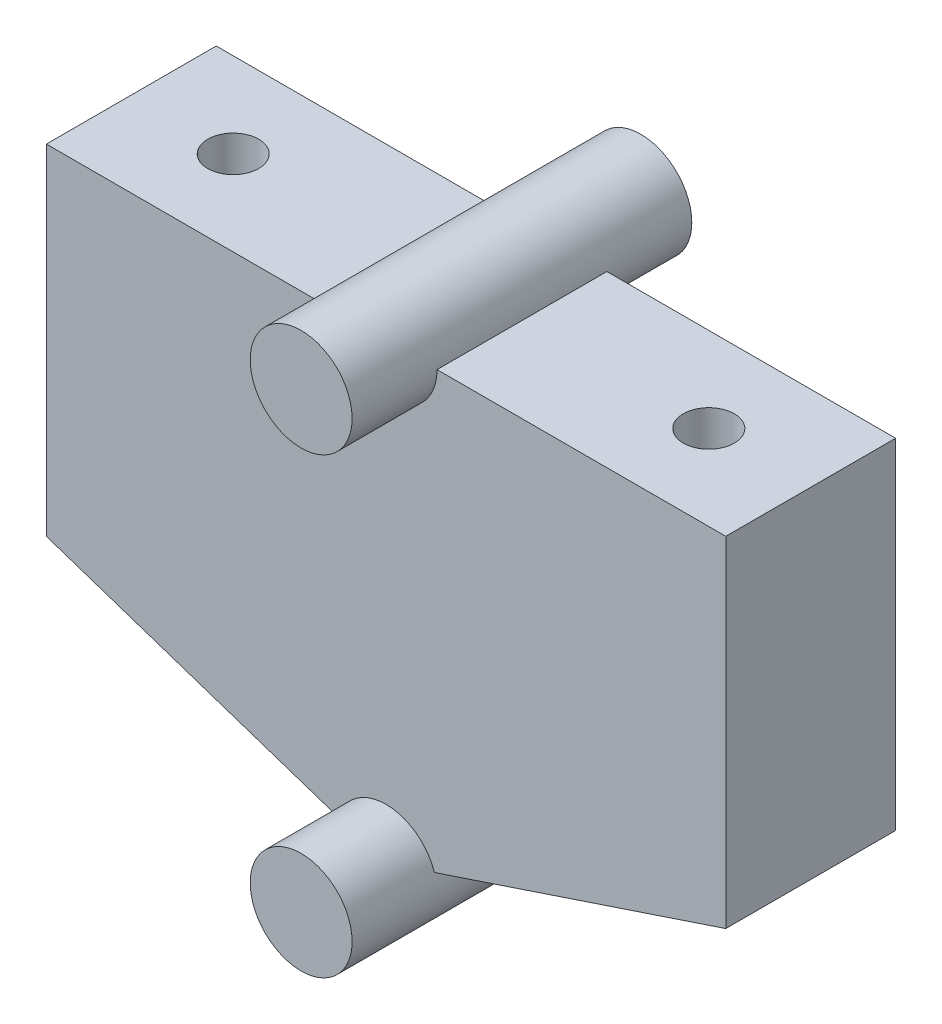
SolidWorks part; units mm, degrees
ref_plane "Front Plane" through (0, 0, 0) normal (0, 0, 1) x (1, 0, 0)
ref_plane "Top Plane" through (0, 0, 0) normal (0, 1, 0) x (1, 0, 0)
ref_plane "Right Plane" through (0, 0, 0) normal (1, 0, 0) x (0, 0, -1)
sketch "Sketch1" plane through (0, 0, 0) normal (0, 0, 1) x (1, 0, 0)
  line L0 (-20, -10) -> (-2.846, -15.718)
  line L1 (-20, 10) -> (20, 10)
  line L2 (-20, 10) -> (-20, -10)
  line L4 (20, 10) -> (20, -10)
  line L5 (-20, 10) -> (20, -10) construction
  line L6 (-20, -10) -> (20, 10) construction
  line L7 (2.846, -15.718) -> (20, -10)
  line L8 (-20, -10) -> (0, -16.6667) construction
  circle A0 centre (0, -16.6667) radius 3
  point P0 (0, 0)
  dimension "D4" = 6
  dimension "D1" = 20
  dimension "D2" = 40
  dimension "D3" = 26.6667
extrude "Boss-Extrude1" add sketch "Sketch1" along normal blind 10 contours A0 L7 L4 L1 L2 L0 region at (0, -1.5827, 0)
extrude "Boss-Extrude2" add sketch "Sketch1<3>" along normal blind 15 and the other way blind 5 contours A0 region at (0, -16.6667, 0)
sketch "Sketch1<3>" plane through (0, 0, 0) normal (0, 0, 1) x (1, 0, 0) same geometry as "Sketch1"
sketch "Sketch2" plane through (0, 10, 0) normal (0, 1, 0) x (1, 0, 0)
  line L0 (-20, 0) -> (20, 0) construction
  line L1 (-20, -10) -> (-20, 0) construction
  line L2 (0, -55) -> (0, 55) construction
  circle A0 centre (-14, -5) radius 1.5
  circle A1 centre (14, -5) radius 1.5
  dimension "D1" = 3
  dimension "D2" = 5
  dimension "D3" = 6
extrude "Cut-Extrude1" cut sketch "Sketch2" against normal through all
sketch "Sketch3" plane through (0, 0, 10) normal (0, 0, 1) x (1, 0, 0)
  line L0 (-20, 10) -> (20, 10) construction
  circle A0 centre (0, 10) radius 3
  dimension "D1" = 6
extrude "Boss-Extrude3" add sketch "Sketch3" along normal blind 5 and the other way blind 15
